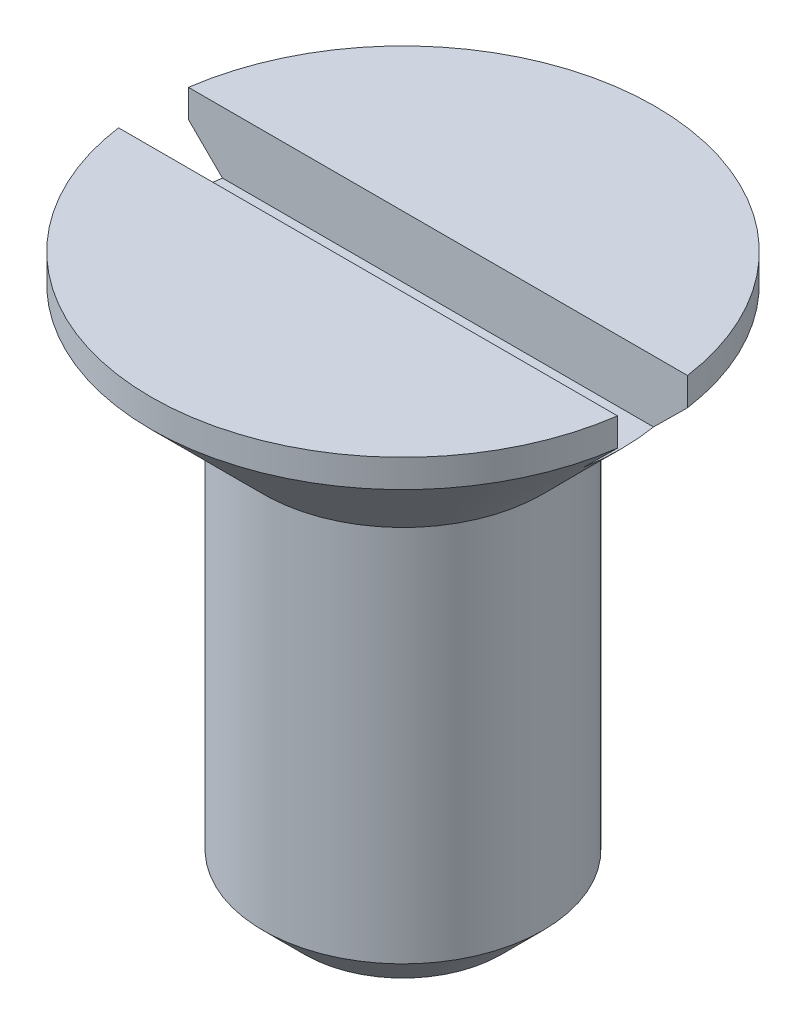
SolidWorks part; units mm, degrees
ref_plane "Спереди" through (0, 0, 0) normal (0, 0, 1) x (1, 0, 0)
ref_plane "Сверху" through (0, 0, 0) normal (0, 1, 0) x (1, 0, 0)
ref_plane "Справа" through (0, 0, 0) normal (1, 0, 0) x (0, 0, -1)
sketch "Эскиз1" plane through (0, 0, 0) normal (0, 0, 1) x (1, 0, 0)
  line L0 (0, 125.7632) -> (0, 0) construction
  line L2 (0, 92.035) -> (0, 72.035)
  line L3 (0, 92.035) -> (9, 92.035)
  line L4 (5, 87.035) -> (5, 72.035)
  line L5 (5, 87.035) -> (9, 91.035)
  line L6 (5, 72.035) -> (0, 72.035)
  line L7 (9, 92.035) -> (9, 91.035)
  dimension "D1" = 9
  dimension "D2" = 20
  dimension "D3" = 5
  dimension "D5" = 5
revolve "Повернуть1" add sketch "Эскиз1" angle 360 about L0
ref_axis "Ось4" through (0, 8.4004, 0) along (0, -1, 0)
sketch "Эскиз13" plane through (0, 92.035, 0) normal (0, 1, 0) x (-1, 0, 0)
  line L1 (9, -1.25) -> (-9, -1.25)
  line L2 (9, -1.25) -> (9, 1.25)
  line L3 (9, 1.25) -> (-9, 1.25)
  line L4 (-9, -1.25) -> (-9, 1.25)
  dimension "D1" = 9
  dimension "D2" = 18
  dimension "D3" = 1.25
  dimension "D4" = 2.5
extrude "Вырез-Вытянуть9" cut sketch "Эскиз13" against normal blind 2.2
chamfer "Фаска1" distance 1.5 angle 45 1 edges at (-5, 72.035, 0)
